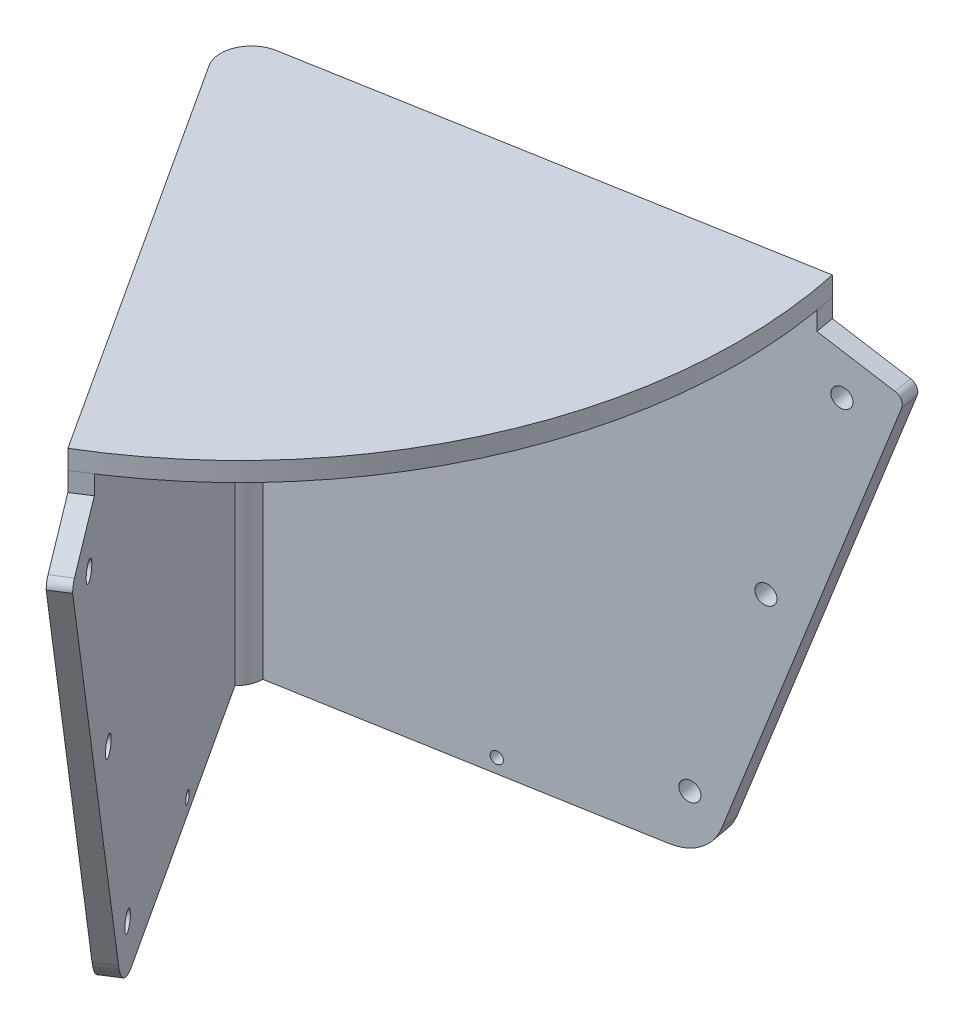
SolidWorks part; units mm, degrees
ref_plane "Front Plane" through (0, 0, 0) normal (0, 0, 1) x (1, 0, 0)
ref_plane "Top Plane" through (0, 0, 0) normal (0, 1, 0) x (1, 0, 0)
ref_plane "Right Plane" through (0, 0, 0) normal (1, 0, 0) x (0, 0, -1)
sketch "Sketch1" plane through (3.1591, 0, 17.9161) normal (-0.1736, 0, -0.9848) x (-0.9848, 0, 0.1736)
  line L0 (90.9457, -13.5582) -> (72.595, -13.5582)
  line L1 (70.2458, -11.9132) -> (62.123, 10.404) construction
  line L2 (70.2458, -11.9132) -> (62.123, 10.404)
  line L3 (62.4218, 11.0448) -> (65.9457, 12.3274)
  line L4 (65.9457, 12.3274) -> (65.9457, 13.3274)
  line L5 (65.9457, 13.3274) -> (66.9457, 13.3274)
  line L10 (90.9457, -12.0582) -> (90.9457, -13.5582)
  line L11 (90.9457, -12.0582) -> (90.9457, 13.3274)
  line L12 (66.9457, 13.3274) -> (90.9457, 13.3274)
  arc A0 (72.595, -13.5582) -> (70.2458, -11.9132) centre (72.595, -11.0582) cw
  arc A1 (70.2458, -11.9132) -> (72.595, -13.5582) centre (72.595, -11.0582) ccw construction
  arc A2 (62.123, 10.404) -> (62.4218, 11.0448) centre (62.5928, 10.575) cw
  circle A7 centre (64.816, 9.7887) radius 0.5
  circle A8 centre (68.2465, -0.5071) radius 0.5
  circle A9 centre (71.677, -10.8029) radius 0.5
  circle A10 centre (80.3897, -12.8204) radius 0.3
  point P23 (0, 0)
  line M17 (90.9457, -12.0582) -> (75.2753, -12.0582)
  line M18 (75.2753, -12.0582) -> (74.5615, -11.3443)
  line M19 (74.5615, -11.3443) -> (66.9457, 9.5799)
  line M20 (66.9457, 9.5799) -> (66.9457, 13.3274)
  line M21 (66.9457, 13.3274) -> (65.9457, 13.3274)
  line M22 (65.9457, 13.3274) -> (65.9457, 12.3274)
  line M23 (65.9457, 12.3274) -> (62.4218, 11.0448)
  arc M24 (62.4218, 11.0448) -> (62.123, 10.404) centre (62.5928, 10.575) ccw
  line M25 (62.123, 10.404) -> (70.2458, -11.9132)
  arc M26 (70.2458, -11.9132) -> (72.595, -13.5582) centre (72.595, -11.0582) ccw
  line M27 (72.595, -13.5582) -> (90.9457, -13.5582)
  line M28 (90.9457, -13.5582) -> (90.9457, -12.0582)
  circle M29 centre (71.677, -10.8029) radius 0.5
  circle M30 centre (80.3897, -12.8204) radius 0.3
  circle M31 centre (68.2465, -0.5071) radius 0.5
  circle M32 centre (64.816, 9.7887) radius 0.5
extrude "Boss-Extrude2" add sketch "Sketch1" along normal blind 1 contours L12 L11 M20 M19 M18 M17 | M28 M17 M18 M19 M20 M21 M22 M23 M24 M25 M26 M27 M30 M32 M31 M29 region at (-66.7699, -2.7564, 30.2465) region at (-76.09, 1.5298, 31.8898)
sketch "Sketch2" plane through (0, -13.5582, 0) normal (0, -1, 0) x (-1, 0, 0)
  line L0 (86.4049, -33.7086) -> (86.4049, -32.7086)
  line L1 (86.8451, -34.721) -> (87.5764, -35.403)
  arc A0 (86.8451, -34.721) -> (86.4049, -33.7086) centre (87.7891, -33.7086) cw
  arc A1 (86.4049, -32.7086) -> (87.5764, -35.403) centre (86.3765, -34.3229) cw
  dimension "D1" = 1
  dimension "D2" = 1
  dimension "D3" = 1
extrude "Boss-Extrude3" add sketch "Sketch2" against normal blind 26.85 separate body
sketch "Sketch3" plane through (-76.9437, 0, 49.9678) normal (-0.8387, 0, 0.5446) x (0.5446, 0, 0.8387)
  line L0 (-18.1798, -13.5582) -> (0.1709, -13.5582)
  line L1 (2.5201, -11.9132) -> (10.6731, 10.575)
  line L2 (10.3441, 11.0448) -> (6.8202, 12.3274)
  line L3 (6.8202, 12.3274) -> (6.8202, 13.3274)
  line L4 (6.8202, 13.3274) -> (5.8202, 13.3274)
  line L5 (5.8202, 13.3274) -> (-18.1798, 13.2918)
  line L6 (-18.1798, 13.2918) -> (-18.1798, -13.5582)
  arc A0 (0.1709, -13.5582) -> (2.5201, -11.9132) centre (0.1709, -11.0582) ccw
  arc A1 (10.6429, 10.404) -> (10.3441, 11.0448) centre (10.1731, 10.575) ccw construction
  arc A2 (10.3441, 11.0448) -> (10.6731, 10.575) centre (10.1731, 10.575) cw
  circle M10 centre (-9.7379, -12.7799) radius 0.3
  circle M11 centre (0.9084, -11.0207) radius 0.5
  circle M12 centre (7.7694, 9.5709) radius 0.5
  circle M13 centre (4.3389, -0.7249) radius 0.5
  line M14 (5.8202, 9.5799) -> (-1.7956, -11.3443)
  line M15 (-1.7956, -11.3443) -> (-2.5094, -12.0582)
  line M16 (-2.5094, -12.0582) -> (-18.1798, -12.0582)
  line M17 (-18.1798, -12.0582) -> (-18.1798, -13.5582)
  line M18 (-18.1798, -13.5582) -> (0.1709, -13.5582)
  arc M19 (0.1709, -13.5582) -> (2.5201, -11.9132) centre (0.1709, -11.0582) ccw
  arc M21 (10.6429, 10.404) -> (10.3441, 11.0448) centre (10.1731, 10.575) ccw
  line M22 (10.3441, 11.0448) -> (6.8202, 12.3274)
  line M23 (6.8202, 12.3274) -> (6.8202, 13.3274)
  line M24 (6.8202, 13.3274) -> (5.8202, 13.3274)
  line M25 (5.8202, 13.3274) -> (5.8202, 9.5799)
extrude "Boss-Extrude4" add sketch "Sketch3" along normal blind 1 contours L5 L6 M16 M15 M14 M25 | L1 M19 M21 M22 M23 M24 M25 M14 M15 M16 M17 M18 M11 M13 M12 M10 region at (-75.9909, -2.768, 51.4349) region at (-81.1394, 1.5202, 43.5069)
sketch "Sketch4" plane through (-0.0108, 13.3188, -0.0166) normal (-0.0008, 1, -0.0012) x (1, 0.0008, 0)
  line L0 (-74.057, -56.2489) -> (-87.6492, -35.3188)
  line L1 (-74.6017, -55.4102) -> (-87.673, -35.2821) construction
  line L2 (-86.5678, -32.7404) -> (-61.9476, -28.3992)
  line L3 (-61.9476, -28.3992) -> (-86.5678, -32.7404) construction
  line L6 (-86.5895, -32.7069) -> (-86.5678, -32.7404) construction
  line L7 (-74.057, -56.2489) -> (-73.2184, -55.7043) construction
  arc A1 (-87.6492, -35.3188) -> (-86.5678, -32.7404) centre (-86.3672, -34.3405) cw
  arc A2 (-74.057, -56.2489) -> (-61.9476, -28.3992) centre (-87.4792, -33.8552) ccw
  ellipse E1 centre (-86.3657, -34.3394) end of major axis (-85.0117, -33.4601) minor radius 1.6145 (-86.3942, -32.7251) -> (-87.6492, -35.3188) ccw construction
  ellipse E2 centre (-87.3798, -33.8976) end of major axis (-65.5743, -19.737) minor radius 26 (-63.3407, -43.8033) -> (-61.7748, -29.3827) ccw construction
extrude "Boss-Extrude5" add sketch "Sketch4" along normal blind 1
